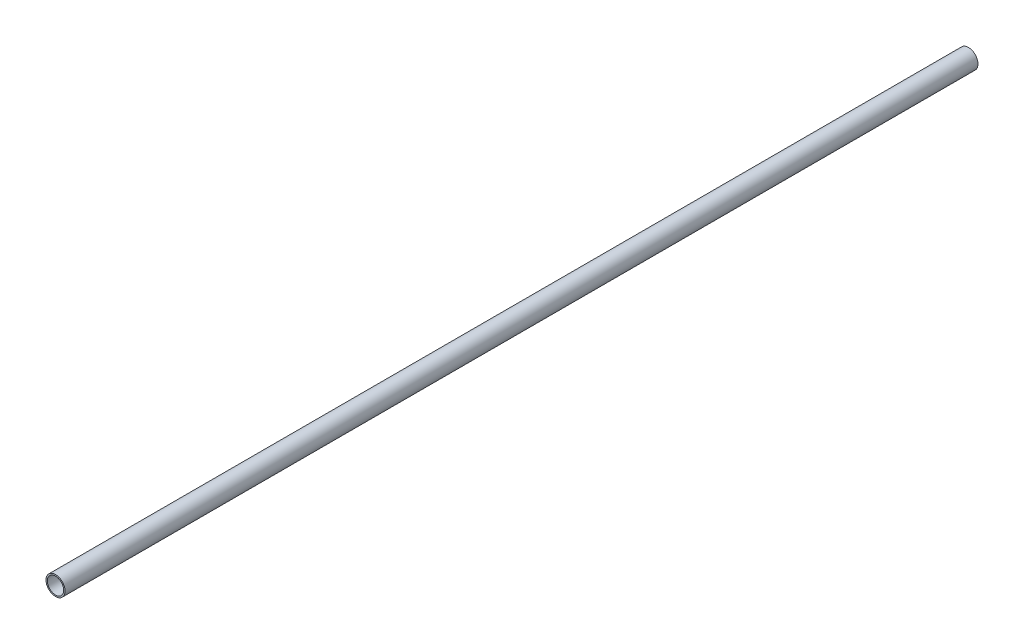
SolidWorks part; units mm, degrees
material "Wing CF"
ref_plane "Front Plane" through (0, 0, 0) normal (0, 0, 1) x (1, 0, 0)
ref_plane "Top Plane" through (0, 0, 0) normal (0, 1, 0) x (1, 0, 0)
ref_plane "Right Plane" through (0, 0, 0) normal (1, 0, 0) x (0, 0, -1)
sketch "Sketch1" plane through (0, 0, 0) normal (0, 0, 1) x (1, 0, 0)
  circle A0 centre (0, 0) radius 7
  circle A1 centre (0, 0) radius 6
  dimension "D1" = 14
  dimension "D2" = 12
extrude "Boss-Extrude1" add sketch "Sketch1" along normal blind 335.28 and the other way blind 335.28
